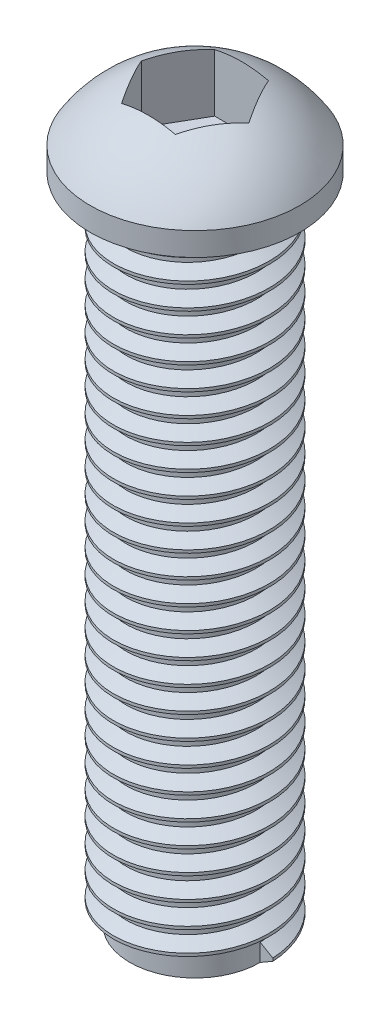
SolidWorks part; units mm, degrees
ref_plane "Front Plane" through (0, 0, 0) normal (0, 0, 1) x (1, 0, 0)
ref_plane "Top Plane" through (0, 0, 0) normal (0, 1, 0) x (1, 0, 0)
ref_plane "Right Plane" through (0, 0, 0) normal (1, 0, 0) x (0, 0, -1)
sketch "Sketch1" plane through (0, 0, 0) normal (0, 1, 0) x (1, 0, 0)
  circle A0 centre (0, 0) radius 1.4
  dimension "D1" = 2.8
extrude "Boss-Extrude1" add sketch "Sketch1" against normal blind 14
sketch "Sketch2" plane through (0, 0, 0) normal (0, 0, 1) x (1, 0, 0)
  line L0 (0, 0) -> (2.25, 0)
  line L1 (2.25, 0) -> (2.25, 0.5)
  line L2 (0, 0) -> (0, 1.75)
  arc A0 (0, 1.75) -> (2.25, 0.5) centre (0, -0.9) cw
  dimension "D1" = 2.25
  dimension "D2" = 0.5
  dimension "D3" = 1.75
revolve "Revolve1" add sketch "Sketch2" angle 360 about L2
sketch "Sketch3" plane through (0, 0, 0) normal (0, 1, 0) x (1, 0, 0)
  line L1 (1.1547, 0) -> (0.5774, 1)
  line L2 (0.5774, 1) -> (-0.5774, 1)
  line L3 (-0.5774, 1) -> (-1.1547, 0)
  line L4 (-1.1547, 0) -> (-0.5774, -1)
  line L5 (-0.5774, -1) -> (0.5774, -1)
  line L6 (0.5774, -1) -> (1.1547, 0)
  circle A0 centre (0, 0) radius 1 construction
  dimension "D1" = 2
  dimension "D2" = 1
extrude "Cut-Extrude1" cut sketch "Sketch3" against normal blind 1.5 from offset 1.75
thread "Thread2" pitch 0.5 method extrude profile "Thread Profile2" start angle 0, offset 0, length 0, pitch 0.5, diameter 2.8
ref_plane "Plane2" through (1.4, -14, 0) normal (0, 0, 1) x (1, 0, 0)
sketch "Thread Profile2" plane through (1.4, -14, 0) normal (0, 0, 1) x (1, 0, 0)
  line L0 (0, 0) -> (0, 0.5) construction
  line L1 (0, 0) -> (0.2706, 0.1562)
  line L2 (0.2706, 0.1562) -> (0.2706, 0.2187)
  line L3 (0.2706, 0.2187) -> (0, 0.375)
  line L4 (0.2706, 0.1875) -> (0, 0.1875) construction
  line L11 (0, 0) -> (0, 0.375)
  point P2 (0, 0)
  dimension "Pitch" = 0.5
  dimension "Profile_Angle" = 60
  dimension "Profile_Land" = 0.0625
  dimension "Profile_Height" = 0.2706
